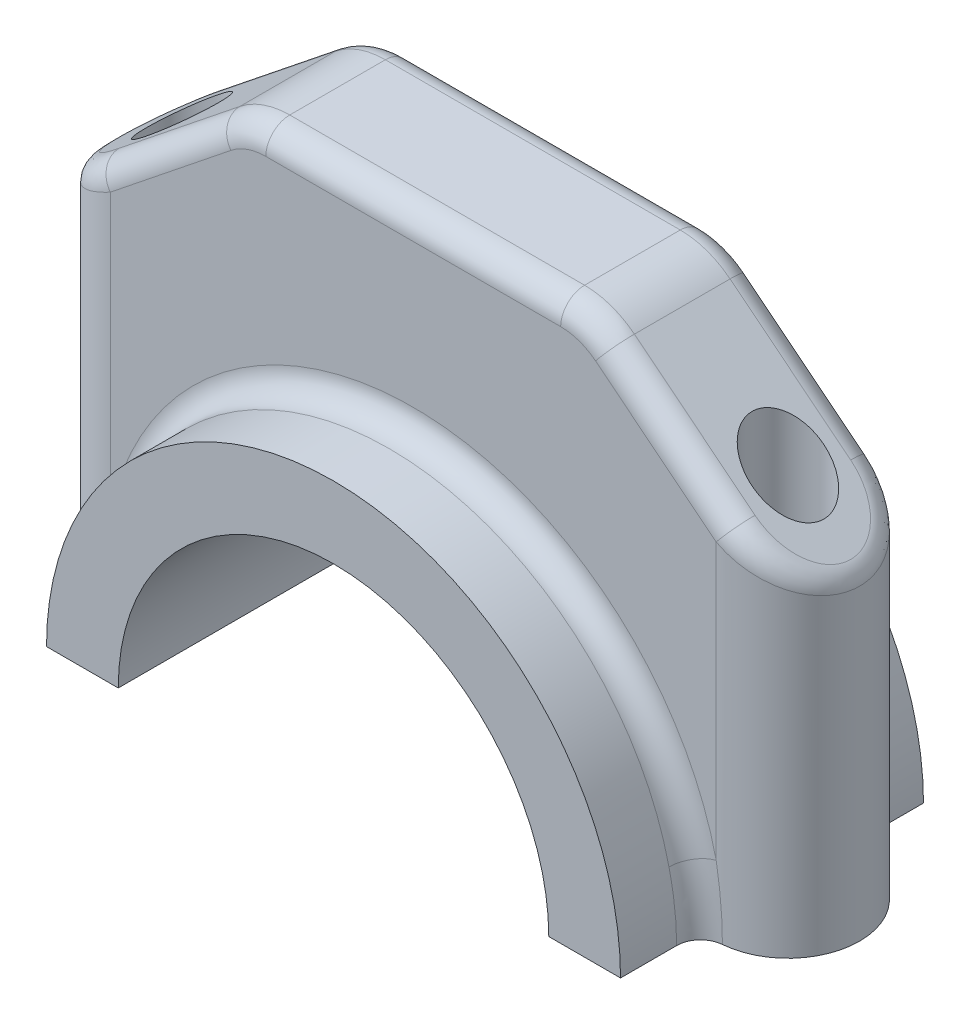
SolidWorks part; units mm, degrees
ref_plane "Front Plane" through (0, 0, 0) normal (0, 0, 1) x (1, 0, 0)
ref_plane "Top Plane" through (0, 0, 0) normal (0, 1, 0) x (1, 0, 0)
ref_plane "Right Plane" through (0, 0, 0) normal (1, 0, 0) x (0, 0, -1)
sketch "Sketch1" plane through (0, 0, 0) normal (0, 0, 1) x (1, 0, 0)
  line L0 (-914.4, 0) -> (-685.8, 0)
  line L1 (685.8, 0) -> (914.4, 0)
  arc A0 (685.8, 0) -> (-685.8, 0) centre (0, 0) ccw
  arc A1 (914.4, 0) -> (-914.4, 0) centre (0, 0) ccw
  dimension "D1" = 1371.6
  dimension "D2" = 1828.8
extrude "Boss-Extrude1" add sketch "Sketch1" along normal mid plane 965.2
ref_plane "Plane1" through (0, 1524, 0) normal (0, -1, 0) x (-1, 0, 0)
sketch "Sketch2" plane through (0, 1524, 0) normal (0, -1, 0) x (-1, 0, 0)
  line L0 (965.2, 0) -> (-965.2, 0) construction
  line L1 (965.2, -228.6) -> (-965.2, -228.6)
  line L2 (965.2, 228.6) -> (-965.2, 228.6)
  arc A0 (965.2, -228.6) -> (965.2, 228.6) centre (965.2, 0) ccw
  arc A1 (-965.2, 228.6) -> (-965.2, -228.6) centre (-965.2, 0) ccw
  point P2 (0, 0)
  dimension "D2" = 228.6
  dimension "D1" = 1930.4
extrude "Boss-Extrude2" add sketch "Sketch2" along normal up to surface (1524 mm away) up to face at (-800.1, 0, 0)
sketch "Sketch3" plane through (0, 0, 228.6) normal (0, 0, 1) x (1, 0, 0)
  line L1 (-685.8, 0) -> (685.8, 0)
  line L2 (-685.8, 0) -> (685.8, 0)
  arc A1 (685.8, 0) -> (-685.8, 0) centre (0, 0) ccw
  arc A2 (685.8, 0) -> (-685.8, 0) centre (0, 0) ccw
  dimension "D1" = 0
extrude "Cut-Extrude1" cut sketch "Sketch3" against normal through all
sketch "Sketch4" plane through (0, 0, 0) normal (0, -1, 0) x (1, 0, 0)
  circle A0 centre (-965.2, 0) radius 114.3
  circle A1 centre (965.2, 0) radius 114.3
  dimension "D1" = 228.6
  dimension "D2" = 228.6
extrude "Cut-Extrude2" cut sketch "Sketch4" against normal through all
sketch "Sketch5" plane through (0, 0, 0) normal (0, 0, 1) x (1, 0, 0)
  line L0 (-1193.8, 1524) -> (-1193.8, 1016)
  line L1 (-1193.8, 1524) -> (-1193.8, 0) construction
  line L2 (-1193.8, 1524) -> (-558.8, 1524)
  line L3 (965.2, 1524) -> (-965.2, 1524) construction
  line L4 (-558.8, 1524) -> (-1193.8, 1016)
  line L5 (0, 0) -> (0, 685.8) construction
  line L6 (558.8, 1524) -> (1193.8, 1016)
  line L7 (1193.8, 1524) -> (558.8, 1524)
  line L8 (1193.8, 1524) -> (1193.8, 1016)
  arc A0 (685.8, 0) -> (-685.8, 0) centre (0, 0) ccw construction
  dimension "D1" = 508
  dimension "D2" = 635
extrude "Cut-Extrude3" cut sketch "Sketch5" against normal through all both and the other way through all
fillet "Fillet1" radius 254 2 edges at (-558.8, 1524, 0) (558.8, 1524, 0)
fillet "Fillet2" radius 76.2 14 edges at (553.7774, 1509.6816, 228.6) (796.7871, 1333.6103, 228.6) (1193.8, 1016, 0) (796.7871, 1333.6103, -228.6) (553.7774, 1509.6816, -228.6) (0, 1524, -228.6) (-553.7774, 1509.6816, -228.6) (-796.7871, 1333.6103, -228.6) (-1193.8, 1016, 0) (-796.7871, 1333.6103, 228.6) (-553.7774, 1509.6816, 228.6) (0, 1524, 228.6) (0, 914.4, -228.6) (0, 914.4, 228.6)
